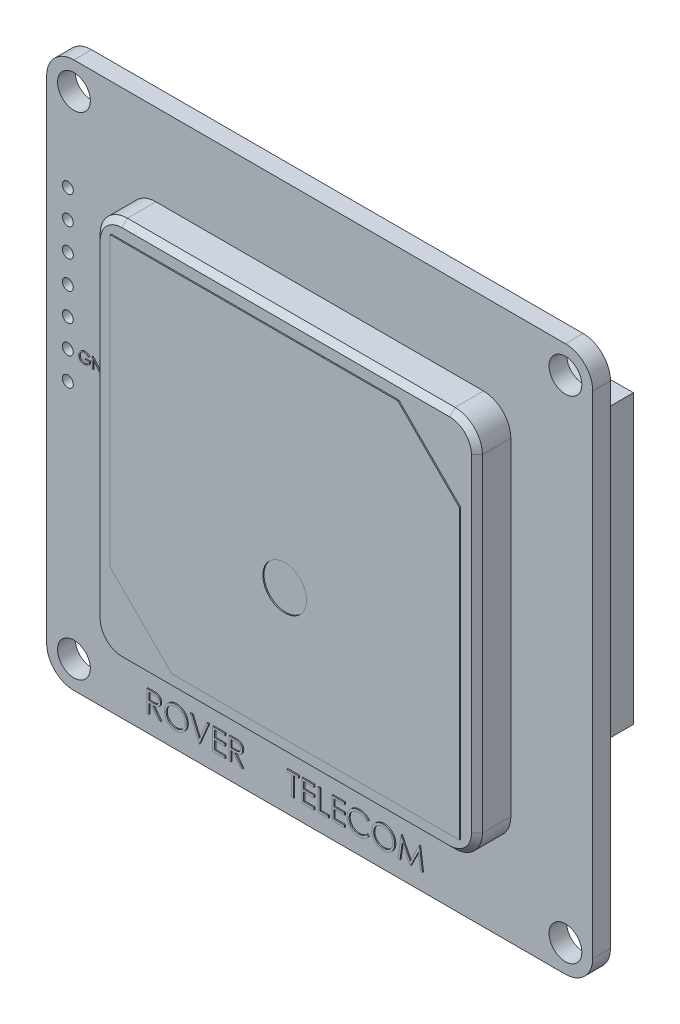
SolidWorks part; units mm, degrees
ref_plane "Ebene vorne" through (0, 0, 0) normal (0, 0, 1) x (1, 0, 0)
ref_plane "Ebene oben" through (0, 0, 0) normal (0, 1, 0) x (1, 0, 0)
ref_plane "Ebene rechts" through (0, 0, 0) normal (1, 0, 0) x (0, 0, -1)
sketch "Sketch1" plane through (0, 0, 0) normal (0, 0, 1) x (1, 0, 0)
  line L0 (25, 25) -> (-25, 25)
  line L1 (-25, 25) -> (-25, -25)
  line L2 (-25, -25) -> (25, -25)
  line L3 (25, -25) -> (25, 25)
  line L4 (-25, 0) -> (25, 0) construction
  line L5 (0, 25) -> (0, -25) construction
  dimension "D1" = 50
  dimension "D2" = 50
extrude "Boss-Extrude1" add sketch "Sketch1" against normal blind 1.62
sketch "Sketch2" plane through (0, 0, 0) normal (0, 0, 1) x (1, 0, 0)
  line L0 (-17.5, 17.5) -> (17.5, 17.5)
  line L1 (17.5, 17.5) -> (17.5, -17.5)
  line L2 (17.5, -17.5) -> (-17.5, -17.5)
  line L3 (-17.5, -17.5) -> (-17.5, 17.5)
  line L4 (0, -17.5) -> (0, 17.5) construction
  line L5 (-17.5, 0) -> (17.5, 0) construction
  dimension "D1" = 35
  dimension "D2" = 35
extrude "Boss-Extrude2" add sketch "Sketch2" along normal blind 3.1
sketch "Sketch3" plane through (0, 0, 3.1) normal (0, 0, 1) x (1, 0, 0)
  line L0 (16, -16) -> (-16, -16)
  line L1 (-16, -16) -> (-16, 16)
  line L2 (-16, 16) -> (16, 16)
  line L3 (16, 16) -> (16, -16)
extrude "Boss-Extrude3" add sketch "Sketch3" along normal blind 0.1
hole_wizard "Ø3.0 (3) Diameter Hole1" positions "Sketch5" profile "Sketch4" hole size "Ø3.0" standard "ANSI Metric" end condition through all
sketch "Sketch5" plane through (0, 0, 0) normal (0, 0, 1) x (1, 0, 0)
  point P0 (22.5, -22.5)
  point P1 (-22.5, 22.5)
  point P2 (22.5, 22.5)
  point P3 (-22.5, -22.5)
sketch "Sketch4" plane through (22.5, -22.5, 0) normal (1, 0, 0) x (0, -1, 0)
  line L0 (0, 0) -> (0, 1.62)
  line L1 (0, 1.62) -> (1.5, 1.62)
  line L2 (1.5, 1.62) -> (1.5, 0)
  line L5 (1.5, 0) -> (0, 0)
  line L11 (0, -6.35) -> (0, 107.95) construction
  dimension "Thru Hole Dia." = 3
  dimension "Thru Hole Depth" = 1.62
hole_wizard "Ø4.0 (4) Diameter Hole1" positions "Sketch7" profile "Sketch6" hole size "Ø4.0" standard "ANSI Metric"
sketch "Sketch7" plane through (0, 0, 3.2) normal (0, 0, 1) x (1, 0, 0)
  point P0 (0, -4)
sketch "Sketch6" plane through (0, -4, 3.2) normal (1, 0, 0) x (0, -1, 0)
  line L0 (0, 0) -> (0, 0.1)
  line L1 (0, 0.1) -> (2, 0.1)
  line L2 (2, 0.1) -> (2, 0)
  line L5 (2, 0) -> (0, 0)
  line L10 (0, 0.1) -> (-2, 0.1) construction
  line L11 (0, -6.35) -> (0, 107.95) construction
  dimension "Hole Dia." = 4
  dimension "Hole Depth" = 0.1
  dimension "Drill Angle" = 180
fillet "Fillet1" radius 2.5 8 edges at (25, -25, -0.81) (25, 25, -0.81) (-25, -25, -0.81) (-25, 25, -0.81) (17.5, -17.5, 1.55) (17.5, 17.5, 1.55) (-17.5, -17.5, 1.55) (-17.5, 17.5, 1.55) tangent propagation no
chamfer "Chamfer1" distance 5.6569 angle 45 2 edges at (-16, -16, 3.15) (16, 16, 3.15)
chamfer "Chamfer2" distance 0.5 angle 45 8 edges at (17.5, 0, 3.1) (16.7678, -16.7678, 3.1) (16.7678, 16.7678, 3.1) (0, -17.5, 3.1) (0, 17.5, 3.1) (-16.7678, -16.7678, 3.1) (-16.7678, 16.7678, 3.1) (-17.5, 0, 3.1)
sketch "Sketch8" plane through (0, 0, -1.62) normal (0, 0, -1) x (-1, 0, 0)
  line L1 (-22, 17.5) -> (4.3, 17.5)
  line L2 (-22, 17.5) -> (-22, -8.8)
  line L3 (-22, -8.8) -> (4.3, -8.8)
  line L4 (4.3, 17.5) -> (4.3, -8.8)
  line L5 (-22.5, 25) -> (22.5, 25) construction
  line L6 (-25, -22.5) -> (-25, 22.5) construction
  dimension "D3" = 7.5
  dimension "D1" = 26.3
  dimension "D2" = 26.3
  dimension "D4" = 3
extrude "Boss-Extrude4" add sketch "Sketch8" along normal blind 5.1
sketch "Sketch9" plane through (0, 0, -1.62) normal (0, 0, -1) x (-1, 0, 0)
  line L0 (22.5, -25) -> (-22.5, -25) construction
  line L1 (-5.96, -19.2) -> (4.78, -19.2)
  line L2 (-5.96, -19.2) -> (-5.96, -25)
  line L3 (-5.96, -25) -> (4.78, -25)
  line L4 (4.78, -19.2) -> (4.78, -25)
  line L5 (-25, -22.5) -> (-25, 22.5) construction
  line L6 (5.98, -19.2) -> (16.72, -19.2)
  line L7 (5.98, -19.2) -> (5.98, -25)
  line L8 (5.98, -25) -> (16.72, -25)
  line L9 (16.72, -19.2) -> (16.72, -25)
  line L10 (-17, -20.6) -> (-9.46, -20.6)
  line L11 (-17, -20.6) -> (-17, -26.2)
  line L12 (-17, -26.2) -> (-9.46, -26.2)
  line L13 (-9.46, -20.6) -> (-9.46, -26.2)
  dimension "D1" = 1.2
  dimension "D2" = 5.6
  dimension "D3" = 7.54
  dimension "D4" = 8
  dimension "D5" = 3.5
  dimension "D6" = 5.8
  dimension "D7" = 10.74
  dimension "D8" = 10.74
  dimension "D9" = 1.2
extrude "Boss-Extrude5" add sketch "Sketch9" along normal blind 4.3 contours L1 L4 L3 L2 | L6 L9 L8 L7
extrude "Boss-Extrude6" add sketch "Sketch9<3>" along normal blind 2.62 contours L10 L13 L12 L11
sketch "Sketch9<3>" plane through (0, 0, -1.62) normal (0, 0, -1) x (-1, 0, 0) same geometry as "Sketch9"
sketch "Sketch10" plane through (0, 0, 0) normal (0, 0, 1) x (1, 0, 0)
  line L0 (-25, 22.5) -> (-25, -22.5) construction
  circle A0 centre (-23.06, 14.6) radius 0.5
  circle A1 centre (-23.06, 12.04) radius 0.5
  circle A2 centre (-23.06, 9.48) radius 0.5
  circle A3 centre (-23.06, 6.92) radius 0.5
  circle A4 centre (-23.06, 4.36) radius 0.5
  circle A5 centre (-23.06, 1.8) radius 0.5
  circle A6 centre (-23.06, -0.76) radius 0.5
  dimension "D1" = 1
  dimension "D2" = 1.94
  dimension "D3" = 10.4
  dimension "D4" = 7
extrude "Cut-Extrude1" cut sketch "Sketch10" against normal through all both and the other way through all
sketch "Sketch11" plane through (0, 0, 0) normal (0, 0, 1) x (1, 0, 0)
  text T0 "GND" font "Century Gothic" height 1
extrude "Boss-Extrude7" add sketch "Sketch11" along normal blind 0.1
sketch "Sketch12" plane through (0, 0, 0) normal (0, 0, 1) x (1, 0, 0)
  text T0 "ROVER     TELECOM" font "Century Gothic" height 2
extrude "Boss-Extrude8" add sketch "Sketch12" along normal blind 0.1
